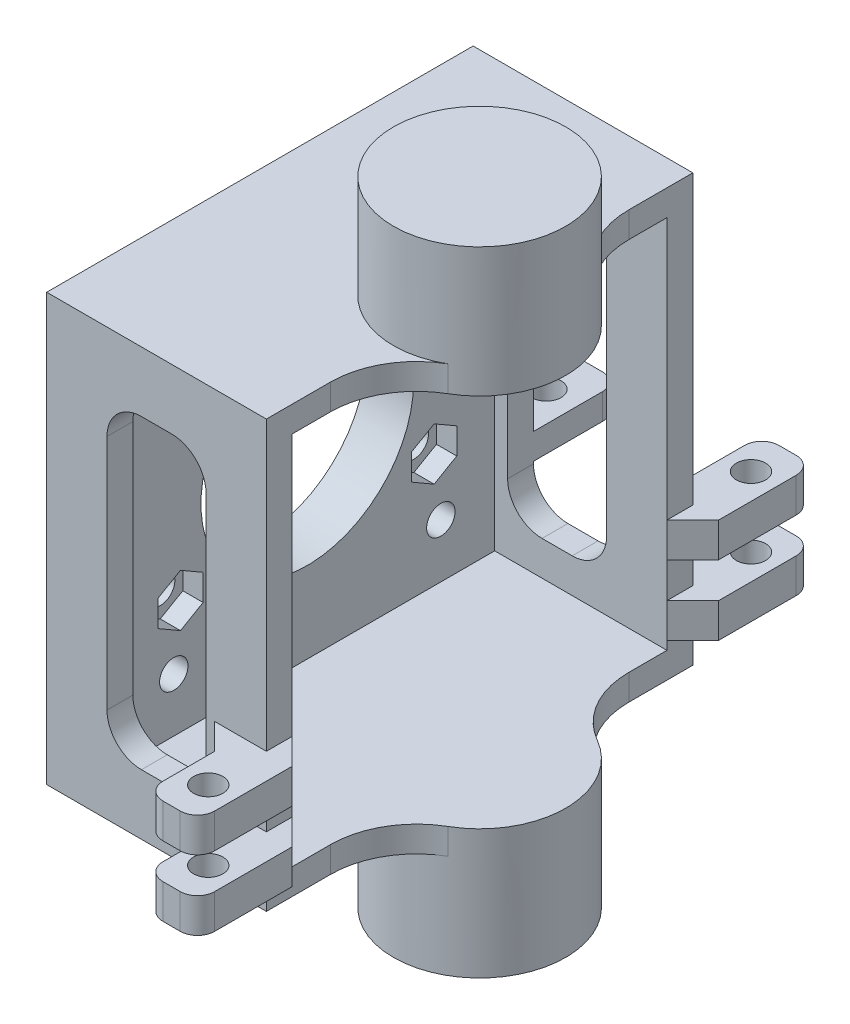
SolidWorks part; units mm, degrees
ref_plane "Alzado" through (0, 0, 0) normal (0, 0, 1) x (1, 0, 0)
ref_plane "Planta" through (0, 0, 0) normal (0, 1, 0) x (1, 0, 0)
ref_plane "Vista lateral" through (0, 0, 0) normal (1, 0, 0) x (0, 0, -1)
sketch "Croquis1" plane through (0, 0, 0) normal (1, 0, 0) x (0, 0, -1)
  line L0 (23.5, -23.5) -> (23.5, 23.5)
  line L1 (-15.5, -15.5) -> (15.5, -15.5) construction
  line L2 (-15.5, -15.5) -> (-15.5, 15.5) construction
  line L3 (-15.5, 15.5) -> (15.5, 15.5) construction
  line L4 (15.5, -15.5) -> (15.5, 15.5) construction
  line L5 (-15.5, -15.5) -> (15.5, 15.5) construction
  line L6 (-15.5, 15.5) -> (15.5, -15.5) construction
  line L7 (-23.5, 23.5) -> (23.5, 23.5)
  line L8 (-23.5, -23.5) -> (-23.5, 23.5)
  line L9 (-23.5, -23.5) -> (23.5, -23.5)
  circle A0 centre (-15.5, 15.5) radius 1.65
  circle A1 centre (15.5, 15.5) radius 1.65
  circle A2 centre (15.5, -15.5) radius 1.65
  circle A3 centre (-15.5, -15.5) radius 1.65
  point P0 (0, 0)
  point P16 (0, 0)
  dimension "D1" = 3.3
  dimension "D2" = 31
  dimension "D3" = 31
  dimension "D5" = 8
  dimension "D4" = 4
extrude "Saliente-Extruir1" add sketch "Croquis1" along normal blind 5.5
sketch "Croquis2" plane through (5.5, 0, 0) normal (1, 0, 0) x (0, 0, -1)
  line L1 (0, 13.9689) -> (2.625, 15.4845)
  line L2 (2.625, 15.4845) -> (2.625, 18.5155)
  line L3 (2.625, 18.5155) -> (0, 20.0311)
  line L4 (0, 20.0311) -> (-2.625, 18.5155)
  line L5 (-2.625, 18.5155) -> (-2.625, 15.4845)
  line L6 (-2.625, 15.4845) -> (0, 13.9689)
  line L24 (14.7224, -11.5311) -> (17.3474, -10.0155)
  line L25 (17.3474, -10.0155) -> (17.3474, -6.9845)
  line L26 (17.3474, -6.9845) -> (14.7224, -5.4689)
  line L27 (14.7224, -5.4689) -> (12.0974, -6.9845)
  line L28 (12.0974, -6.9845) -> (12.0974, -10.0155)
  line L29 (12.0974, -10.0155) -> (14.7224, -11.5311)
  line L30 (-17.3474, -6.9845) -> (-17.3474, -10.0155)
  line L31 (-17.3474, -10.0155) -> (-14.7224, -11.5311)
  line L32 (-14.7224, -11.5311) -> (-12.0974, -10.0155)
  line L33 (-12.0974, -10.0155) -> (-12.0974, -6.9845)
  line L34 (-12.0974, -6.9845) -> (-14.7224, -5.4689)
  line L35 (-14.7224, -5.4689) -> (-17.3474, -6.9845)
  circle A0 centre (0, 0) radius 17 construction
  circle A1 centre (0, 17) radius 2.625 construction
  point P26 (0, 0)
  dimension "D1" = 34
  dimension "D3" = 5.25
  dimension "D2" = 3
extrude "Cortar-Extruir1" cut sketch "Croquis2" against normal blind 2.35
sketch "Croquis7" plane through (5.5, 0, 0) normal (1, 0, 0) x (0, 0, -1)
  circle A0 centre (0, 0) radius 12.35
  dimension "D1" = 24.7
extrude "Cortar-Extruir2" cut sketch "Croquis7" against normal up to surface (5.5 mm away) up to face at (0, 0, 0)
sketch "Croquis8" plane through (5.5, 0, 0) normal (1, 0, 0) x (0, 0, -1)
  circle A0 centre (0, 17) radius 1.7
  circle A1 centre (14.7224, -8.5) radius 1.7
  circle A2 centre (-14.7224, -8.5) radius 1.7
  point P9 (0, 0)
  dimension "D1" = 3.4
  dimension "D2" = 3
extrude "Cortar-Extruir3" cut sketch "Croquis8" against normal up to surface (5.5 mm away) up to face at (0, 0, -12.35)
sketch "Croquis9" plane through (0, 0, 0) normal (1, 0, 0) x (0, 0, -1)
  line L0 (-24.75, -24.75) -> (24.75, -24.75)
  line L1 (-21.75, 21.75) -> (21.75, 21.75)
  line L2 (-21.75, 21.75) -> (-21.75, -21.75)
  line L3 (-21.75, -21.75) -> (21.75, -21.75)
  line L4 (21.75, 21.75) -> (21.75, -21.75)
  line L5 (-21.75, 21.75) -> (21.75, -21.75) construction
  line L6 (-21.75, -21.75) -> (21.75, 21.75) construction
  line L7 (24.75, 24.75) -> (24.75, -24.75)
  line L8 (-24.75, 24.75) -> (24.75, 24.75)
  line L9 (-24.75, 24.75) -> (-24.75, -24.75)
  point P0 (0, 0)
  dimension "D1" = 43.5
  dimension "D2" = 3
extrude "Saliente-Extruir2" add sketch "Croquis9" along normal blind 25.5
sketch "Croquis10" plane through (0, 21.75, 0) normal (0, 1, 0) x (1, 0, 0)
  line L0 (25.5, 24.75) -> (25.5, -24.75) construction
  circle A0 centre (25.5, 0) radius 10
  dimension "D1" = 20
extrude "Saliente-Extruir3" add sketch "Croquis10" along normal blind 15
mirror "Simetría1" about plane through (0, 0, 0) normal (0, 1, 0) of "Saliente-Extruir3"
sketch "Croquis11" plane through (0, 0, -24.75) normal (0, 0, -1) x (-1, 0, 0)
  line L12 (-7, -17.75) -> (-7, 17.75)
  line L13 (-7, 17.75) -> (-18.5, 17.75)
  line L14 (-18.5, 17.75) -> (-18.5, -17.75)
  line L15 (-18.5, -17.75) -> (-7, -17.75)
  line L16 (-7, -13.75) -> (-7, 13.75)
  line L17 (-11, 17.75) -> (-14.5, 17.75)
  line L18 (-18.5, 13.75) -> (-18.5, -13.75)
  line L19 (-14.5, -17.75) -> (-11, -17.75)
  arc A0 (-7, 13.75) -> (-11, 17.75) centre (-11, 13.75) ccw
  arc A1 (-14.5, 17.75) -> (-18.5, 13.75) centre (-14.5, 13.75) ccw
  arc A2 (-18.5, -13.75) -> (-14.5, -17.75) centre (-14.5, -13.75) ccw
  arc A3 (-7, -13.75) -> (-11, -17.75) centre (-11, -13.75) cw
  dimension "D2" = 4
  dimension "D1" = 7
extrude "Cortar-Extruir4" cut sketch "Croquis11" against normal up to surface (49.5 mm away) up to face at (12.75, 0, 24.75)
fillet "Redondeo1" radius 10 4 edges at (25.5, 23.25, 10) (25.5, -23.25, 10) (25.5, 23.25, -10) (25.5, -23.25, -10)
ref_plane "Plano1" through (0, -20.75, 0) normal (0, -1, 0) x (-1, 0, 0)
sketch "Croquis13" plane through (0, -20.75, 0) normal (0, -1, 0) x (1, 0, 0)
  line L0 (25.5, 0) -> (25.5, -35) construction
  line L1 (28.5, -24.75) -> (22.5, -24.75)
  line L2 (25.5, -24.75) -> (0, -24.75) construction
  line L3 (22.5, -24.75) -> (22.5, -35.75)
  line L4 (22.5, -35.75) -> (27.0226, -35.75)
  line L5 (28.5, -24.75) -> (28.5, -35.75)
  line L6 (28.5, -35.75) -> (23.9774, -35.75)
  circle A0 centre (25.5, 0) radius 10 construction
  circle A1 centre (25.5, 0) radius 10 construction
  circle A2 centre (25.5, 0) radius 35 construction
  circle A3 centre (25.5, 0) radius 31.5 construction
  circle A4 centre (25.5, -31.5) radius 1.7
  point P16 (25.5, -24.75)
  point P18 (25.5, -24.75)
  dimension "D1" = 70
  dimension "D3" = 3.4
  dimension "D4" = 6
  dimension "D5" = 11
  dimension "D2" = 3.5
extrude "Saliente-Extruir5" add sketch "Croquis13" against normal blind 12.1 contours L6 L5 L1 L3 L4 A4 region at (28.3747, -20.75, -30.25)
sketch "Croquis14" plane through (0, 0, -24.75) normal (0, 0, -1) x (-1, 0, 0)
  line L0 (-28.5, -14.7) -> (-22.5, -14.7) construction
  line L1 (-28.5, -8.65) -> (-28.5, -20.75) construction
  line L2 (-22.5, -8.65) -> (-22.5, -20.75) construction
  line L3 (-28.5, -16.75) -> (-22.5, -16.75)
  line L5 (-28.5, -12.65) -> (-28.5, -16.75)
  line L6 (-22.5, -12.65) -> (-22.5, -16.75)
  line L7 (-28.5, -12.65) -> (-22.5, -12.65)
  dimension "D1" = 4.1
extrude "Cortar-Extruir5" cut sketch "Croquis14" along normal up to surface (11 mm away) up to face at (25.5, -14.7, -35.75)
mirror "Simetría2" about plane through (0, 0, 0) normal (0, 0, 1) of "Cortar-Extruir5", "Saliente-Extruir5"
chamfer "Chaflán1" distance 3 angle 45 8 edges at (22.5, -18.75, -24.75) (22.5, -10.65, -24.75) (22.5, -10.65, 24.75) (22.5, -18.75, 24.75) (25.5, -10.65, 24.75) (25.5, -18.75, 24.75) (25.5, -18.75, -24.75) (25.5, -10.65, -24.75)
sketch "Croquis15" plane through (0, 0, -24.75) normal (0, 0, -1) x (-1, 0, 0)
  line L0 (0, 0) -> (-14.3445, 0) construction
  line L1 (0, -24.75) -> (0, 24.75) construction
  line L2 (0, 13.5) -> (-7, 13.5)
  line L3 (0, 13.5) -> (0, 10.5)
  line L4 (0, 10.5) -> (-7, 10.5)
  line L5 (-7, 13.5) -> (-7, 10.5)
  line L6 (-7, -13.75) -> (-7, 13.75) construction
  line L7 (0, -10.5) -> (-7, -10.5)
  line L8 (-7, -13.5) -> (-7, -10.5)
  line L9 (0, -13.5) -> (-7, -13.5)
  line L10 (0, -13.5) -> (0, -10.5)
  dimension "D1" = 3
  dimension "D2" = 21
extrude "Saliente-Extruir6" add sketch "Croquis15" along normal blind 10
sketch "Croquis16" plane through (0, -13.5, 0) normal (0, -1, 0) x (1, 0, 0)
  line L0 (3.5, -24.75) -> (3.5, -34.75) construction
  line L1 (7, -24.75) -> (0, -24.75) construction
  line L2 (7, -34.75) -> (0, -34.75) construction
  line L3 (0, -29.75) -> (7, -29.75) construction
  line L4 (0, -34.75) -> (0, -24.75) construction
  line L5 (7, -34.75) -> (7, -24.75) construction
  circle A0 centre (3.5, -29.75) radius 1.7
  dimension "D1" = 3.4
extrude "Cortar-Extruir6" cut sketch "Croquis16" against normal up to surface (27 mm away) contours A0 up to face at (3.5, 13.5, -29.75)
fillet "Redondeo2" radius 2 4 edges at (0, -12, -34.75) (7, -12, -34.75) (7, 12, -34.75) (0, 12, -34.75)
fillet "Redondeo4" radius 2 6 edges at (28.5, -18.75, -35.75) (28.5, -18.75, 35.75) (22.5, -18.75, 35.75) (22.5, -18.75, -35.75) (22.5, -10.65, -35.75) (28.5, -10.65, -35.75)
sketch "Croquis18" plane through (0, 0, 0) normal (-1, 0, 0) x (0, 0, 1)
  circle A0 centre (-15.5, 15.5) radius 3.25
  circle A1 centre (15.5, 15.5) radius 3.25
  circle A2 centre (15.5, -15.5) radius 3.25
  circle A3 centre (-15.5, -15.5) radius 3.25
  point P12 (0, 0)
  dimension "D1" = 6.5
  dimension "D2" = 4
extrude "Cortar-Extruir7" cut sketch "Croquis18" against normal blind 2.5
